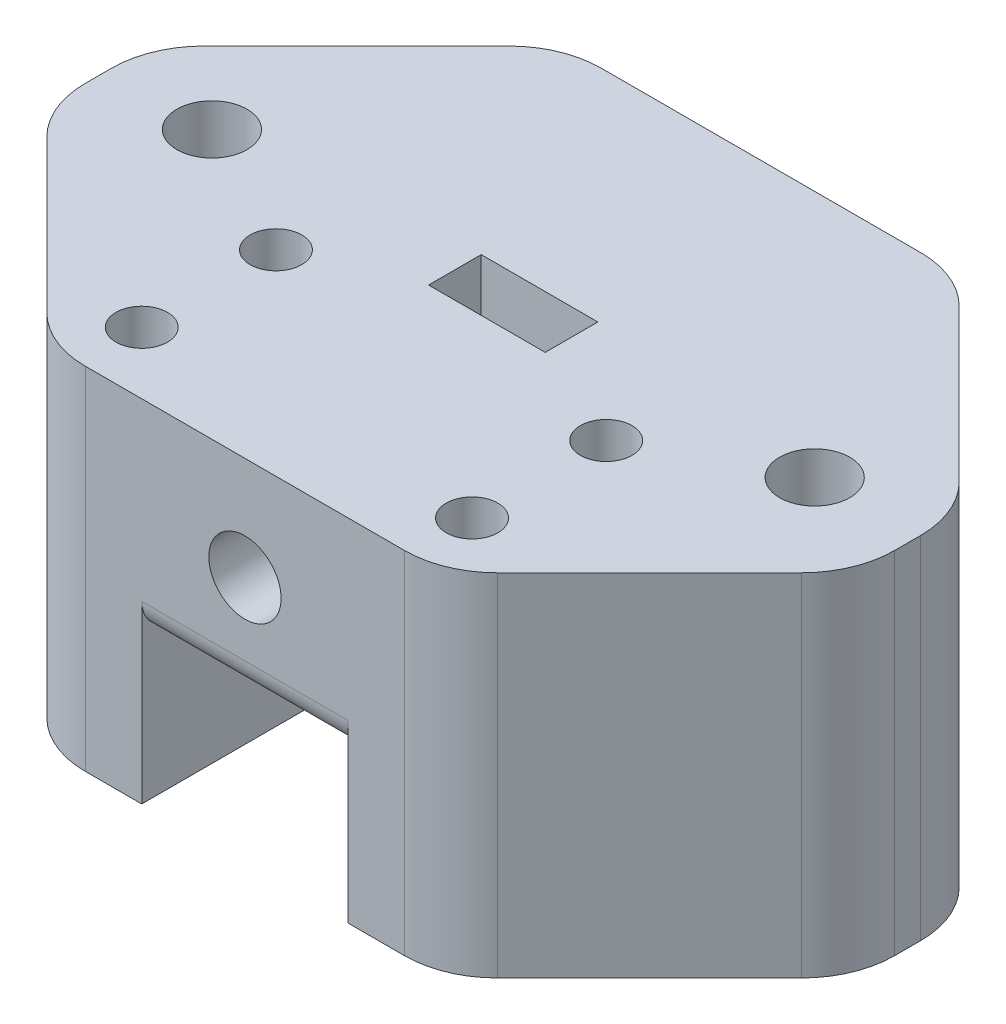
SolidWorks part; units mm, degrees
material "ABS PC"
ref_plane "Front Plane" through (0, 0, 0) normal (0, 0, 1) x (1, 0, 0)
ref_plane "Top Plane" through (0, 0, 0) normal (0, 1, 0) x (1, 0, 0)
ref_plane "Right Plane" through (0, 0, 0) normal (1, 0, 0) x (0, 0, -1)
sketch "Sketch1" plane through (0, 0, 0) normal (0, 1, 0) x (1, 0, 0)
  line L0 (0, 0) -> (0, 25)
  line L1 (0, 0) -> (39.2, 0)
  line L2 (0, 25) -> (39.2, 25)
  line L3 (39.2, 0) -> (39.2, 25)
  dimension "D1" = 39.2
  dimension "D2" = 25
extrude "Boss-Extrude1" add sketch "Sketch1" along normal blind 10
hole_wizard "Ø3.5 (3.5) Diameter Hole1" positions "Sketch8" profile "Sketch7" hole size "Ø3.5" standard "ANSI Metric" end condition through all
sketch "Sketch8" plane through (0, 0, -25) normal (0, 0, -1) x (-1, 0, 0)
  line L2 (0, 10) -> (0, 0) construction
  line L3 (-39.2, 0) -> (0, 0) construction
  point P0 (-19.6, 5)
  point P15 (-19.6, 0)
  dimension "D1" = 19.6
  dimension "D2" = 5
sketch "Sketch7" plane through (19.6, 5, -25) normal (1, 0, 0) x (0, 1, 0)
  line L0 (0, 0) -> (0, 25)
  line L1 (0, 25) -> (1.75, 25)
  line L2 (1.75, 25) -> (1.75, 0)
  line L5 (1.75, 0) -> (0, 0)
  line L11 (0, -6.35) -> (0, 107.95) construction
  dimension "Thru Hole Dia." = 3.5
  dimension "Thru Hole Depth" = 25
sketch "Sketch9" plane through (0, 0, 0) normal (0, -1, 0) x (1, 0, 0)
  line L0 (39.2, -25) -> (39.2, 0)
  line L1 (39.2, -25) -> (24.6, -25)
  line L2 (39.2, 0) -> (24.6, 0)
  line L3 (24.6, -25) -> (24.6, 0)
  line L4 (0, -25) -> (0, 0)
  line L5 (0, -25) -> (14.6, -25)
  line L6 (0, 0) -> (14.6, 0)
  line L7 (14.6, -25) -> (14.6, 0)
  dimension "D1" = 10
  dimension "D2" = 14.6
extrude "Boss-Extrude2" add sketch "Sketch9" along normal blind 7
sketch "Sketch10" plane through (0, 10, 0) normal (0, 1, 0) x (1, 0, 0)
  line L0 (16.775, 11.72) -> (22.425, 11.72)
  line L1 (16.775, 11.72) -> (16.775, 14.27)
  line L2 (22.425, 11.72) -> (22.425, 14.27)
  line L3 (16.775, 14.27) -> (22.425, 14.27)
  line L4 (0, 25) -> (0, 0) construction
  line L5 (39.2, 25) -> (0, 25) construction
  dimension "D1" = 5.65
  dimension "D2" = 2.55
  dimension "D3" = 16.775
  dimension "D4" = 10.73
extrude "Cut-Extrude4" cut sketch "Sketch10" against normal blind 10
hole_wizard "Ø2.5 (2.5) Diameter Hole1" positions "Sketch12" profile "Sketch11" hole size "Ø2.5" standard "ANSI Metric"
sketch "Sketch12" plane through (0, 10, 0) normal (0, 1, 0) x (1, 0, 0)
  line L0 (0, 0) -> (39.2, 0) construction
  line L1 (39.2, 0) -> (39.2, 25) construction
  point P0 (11.6, 3)
  point P2 (27.6, 3)
  point P4 (27.6, 9.5)
  point P6 (11.6, 9.5)
  dimension "D1" = 3
  dimension "D2" = 6.5
  dimension "D3" = 16
  dimension "D4" = 11.6
sketch "Sketch11" plane through (11.6, 10, -3) normal (1, 0, 0) x (0, 0, 1)
  line L0 (0, 0) -> (0, 7.7511)
  line L1 (0, 7.7511) -> (1.25, 7)
  line L2 (1.25, 7) -> (1.25, 0)
  line L5 (1.25, 0) -> (0, 0)
  line L10 (0, 7.7511) -> (-1.25, 7) construction
  line L11 (0, -6.35) -> (0, 107.95) construction
  dimension "Hole Dia." = 2.5
  dimension "Hole Depth" = 7
  dimension "Drill Angle" = 118
hole_wizard "Ø3.4 (3.4) Diameter Hole1" positions "Sketch3" profile "Sketch2" hole size "Ø3.4" standard "ANSI Metric" end condition through all
sketch "Sketch3" plane through (0, 10, 0) normal (0, 1, 0) x (1, 0, 0)
  line L0 (0, 25) -> (0, 0) construction
  line L1 (39.2, 0) -> (39.2, 25) construction
  line L3 (39.2, 25) -> (0, 25) construction
  point P0 (34.2, 13)
  point P2 (5, 13)
  dimension "D1" = 5
  dimension "D2" = 5
  dimension "D4" = 12
sketch "Sketch2" plane through (34.2, 10, -13) normal (1, 0, 0) x (0, 0, 1)
  line L0 (0, 0) -> (0, 17)
  line L1 (0, 17) -> (1.7, 17)
  line L2 (1.7, 17) -> (1.7, 0)
  line L5 (1.7, 0) -> (0, 0)
  line L11 (0, -6.35) -> (0, 107.95) construction
  dimension "Thru Hole Dia." = 3.4
  dimension "Thru Hole Depth" = 17
chamfer "Chamfer1" distance 10 angle 45 4 edges at (0, 1.5, -25) (0, 1.5, 0) (39.2, 1.5, 0) (39.2, 1.5, -25)
fillet "Fillet5" radius 4.5 8 edges at (29.2, 1.5, 0) (10, 1.5, 0) (0, 1.5, -10) (0, 1.5, -15) (10, 1.5, -25) (29.2, 1.5, -25) (39.2, 1.5, -10) (39.2, 1.5, -15)
fillet "Fillet6" radius 1.5 1 edges
